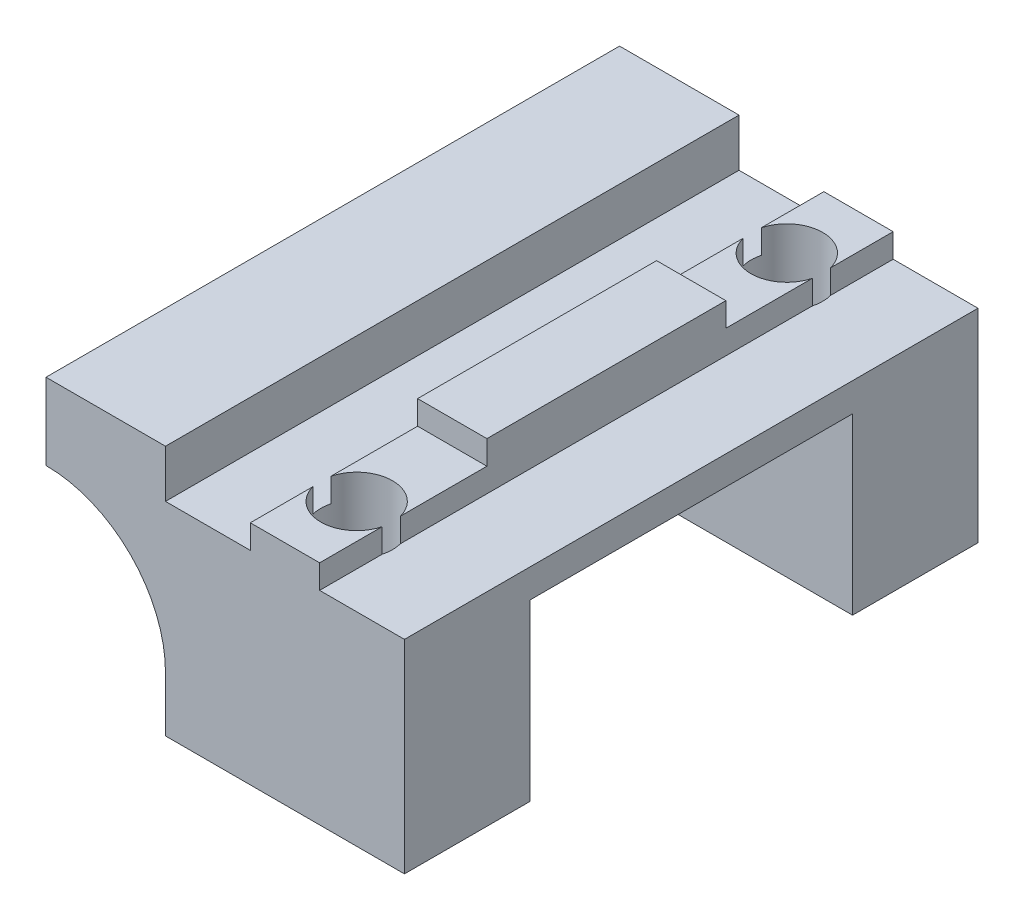
SolidWorks part; units mm, degrees
ref_plane "Front Plane" through (0, 0, 0) normal (0, 0, 1) x (1, 0, 0)
ref_plane "Top Plane" through (0, 0, 0) normal (0, 1, 0) x (1, 0, 0)
ref_plane "Right Plane" through (0, 0, 0) normal (1, 0, 0) x (0, 0, -1)
sketch "Sketch1" plane through (0, 0, 0) normal (0, 0, 1) x (1, 0, 0)
  line L0 (-5, 8.5) -> (-5, 0)
  line L1 (-5, 0) -> (5, 0)
  line L2 (5, 0) -> (5, 8.5)
  line L3 (5, 8.5) -> (1.45, 8.5)
  line L4 (1.45, 8.5) -> (1.45, 10.5)
  line L5 (1.45, 10.5) -> (-1.45, 10.5)
  line L6 (-1.45, 10.5) -> (-1.45, 8.5)
  line L7 (-1.45, 8.5) -> (-5, 8.5)
  point P0 (0, 0)
  point P8 (0, 0)
  dimension "D1" = 10
  dimension "D2" = 2
  dimension "D3" = 2.9
  dimension "D4" = 8.5
extrude "Main" add sketch "Sketch1" along normal mid plane 24
sketch "Sketch2" plane through (0, 10.5, 0) normal (0, 1, 0) x (1, 0, 0)
  line L1 (-1.45, -12) -> (-5, -12) construction
  line L2 (1.45, 12) -> (-1.45, 12) construction
  circle A0 centre (0, -9) radius 1.5
  circle A1 centre (0, 9) radius 1.5
  point P7 (-3.225, -12)
  point P8 (0, 0)
  point P9 (0, 12.0772)
  dimension "D1" = 3
  dimension "D2" = 3
  dimension "D3" = 3
extrude "HoleMakerBeamFix" cut sketch "Sketch2" against normal through all
sketch "Sketch3" plane through (0, 0, 0) normal (0, -1, 0) x (-1, 0, 0)
  line L0 (-5, -12) -> (-5, 12) construction
  line L1 (-5, -6.75) -> (5, -6.75)
  line L2 (-5, -6.75) -> (-5, 6.75)
  line L3 (-5, 6.75) -> (5, 6.75)
  line L4 (5, -6.75) -> (5, 6.75)
  line L5 (5, -12) -> (5, 12) construction
  point P8 (0, 0)
  point P9 (5, 0)
  dimension "D1" = 13.5
extrude "MainConnectorHole" cut sketch "Sketch3" against normal blind 7.3
sketch "Sketch4" plane through (0, 7.3, 0) normal (0, -1, 0) x (-1, 0, 0)
  line L1 (5, -12) -> (10, -12)
  line L2 (5, -12) -> (5, 12)
  line L3 (5, 12) -> (10, 12)
  line L4 (10, -12) -> (10, 12)
  point P5 (5, -2)
  point P7 (5, 12)
  point P9 (5, -12)
  dimension "D1" = 5
extrude "ConnectorSupportExtension" add sketch "Sketch4" against normal up to surface (3.2 mm away) up to face at (0, 10.5, 0)
sketch "Sketch5" plane through (0, 7.3, 0) normal (0, -1, 0) x (-1, 0, 0)
  line L0 (10, -12) -> (10, 12) construction
  line L1 (8.8, -4.25) -> (7, -4.25)
  line L2 (8.8, -4.25) -> (8.8, 4.25)
  line L3 (8.8, 4.25) -> (7, 4.25)
  line L4 (7, -4.25) -> (7, 4.25)
  line L5 (-5, 6.75) -> (-5, -6.75) construction
  point P4 (8.8, 0)
  point P5 (0, 0)
  point P6 (10, 0)
  dimension "D1" = 8.5
  dimension "D2" = 1.8
  dimension "D3" = 12
extrude "ConnectorRailHole" cut sketch "Sketch5" against normal blind 1.5
sketch "Sketch6" plane through (0, 10.5, 0) normal (0, 1, 0) x (1, 0, 0)
  line L0 (1.45, -8.6159) -> (1.45, 8.6159) construction
  line L1 (-1.45, 12) -> (1.45, 12)
  line L2 (-1.45, 12) -> (-1.45, 5)
  line L3 (-1.45, 5) -> (1.45, 5)
  line L4 (1.45, 12) -> (1.45, 5)
  line L6 (-1.45, -12) -> (1.45, -12)
  line L7 (-1.45, -12) -> (-1.45, -5)
  line L8 (-1.45, -5) -> (1.45, -5)
  line L9 (1.45, -12) -> (1.45, -5)
  point P12 (1.45, -5)
  dimension "D1" = 7
extrude "Cut-Extrude4" cut sketch "Sketch6" against normal blind 1
fillet "Fillet3" radius 5 2 edges at (-5, 7.3, -9.375) (-5, 7.3, 9.375)
